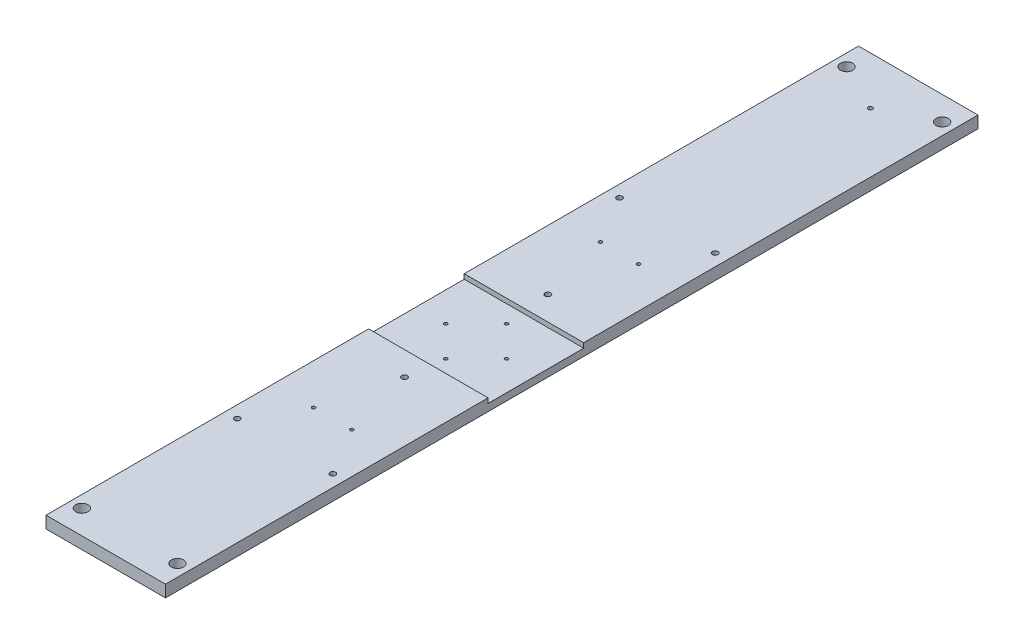
SolidWorks part; units mm, degrees
ref_plane "Front" through (0, 0, 0) normal (0, 0, 1) x (1, 0, 0)
ref_plane "Top" through (0, 0, 0) normal (0, 1, 0) x (1, 0, 0)
ref_plane "Right" through (0, 0, 0) normal (1, 0, 0) x (0, 0, -1)
sketch "Sketch1" plane through (0, 0, 0) normal (0, 1, 0) x (1, 0, 0)
  line L1 (0, 0) -> (63.5, 0)
  line L2 (0, 0) -> (0, 431.8)
  line L3 (0, 431.8) -> (63.5, 431.8)
  line L4 (63.5, 0) -> (63.5, 431.8)
  dimension "D1" = 431.8
  dimension "D2" = 63.5
extrude "Boss-Extrude1" add sketch "Sketch1" along normal blind 6.35
sketch "Sketch3" plane through (0, 6.35, 0) normal (0, 1, 0) x (1, 0, 0)
  line L0 (0, 0) -> (63.5, 0) construction
  line L1 (0, 431.8) -> (0, 0) construction
  line L2 (31.75, 431.8) -> (31.75, 0) construction
  line L3 (63.5, 431.8) -> (0, 431.8) construction
  line L6 (0, 165.1) -> (0, 228.6)
  line L9 (0, 196.85) -> (139.7, 196.85) construction
  circle A0 centre (3.175, 3.175) radius 1.1303
  circle A1 centre (3.175, 161.925) radius 1.1303
  circle A2 centre (3.175, 390.525) radius 1.1303
  circle A3 centre (3.175, 231.775) radius 1.1303
  circle A4 centre (60.325, 3.175) radius 1.1303
  circle A5 centre (60.325, 161.925) radius 1.1303
  circle A6 centre (60.325, 231.775) radius 1.1303
  circle A7 centre (60.325, 390.525) radius 1.1303
  dimension "D1" = 2.2606
  dimension "D2" = 3.175
  dimension "D3" = 3.175
  dimension "D5" = 63.5
  dimension "D4" = 2
sketch "Sketch6" plane through (0, 6.35, 0) normal (0, 1, 0) x (1, 0, 0)
  line L0 (63.5, 431.8) -> (0, 431.8) construction
  line L1 (0, 431.8) -> (0, 0) construction
  line L2 (31.75, 431.8) -> (31.75, 0) construction
  line L3 (0, 0) -> (63.5, 0) construction
  line L4 (31.75, 215.9) -> (94.2364, 215.9) construction
  circle A0 centre (6.35, 419.1) radius 3.2639
  circle A1 centre (57.15, 419.1) radius 3.2639
  circle A4 centre (57.15, 12.7) radius 3.2639
  circle A5 centre (6.35, 12.7) radius 3.2639
  point P13 (31.75, 215.9)
  dimension "D1" = 6.5278
  dimension "D2" = 12.7
  dimension "D3" = 6.35
extrude "Cut-Extrude9" cut sketch "Sketch6" against normal through all
sketch "Sketch7" plane through (0, 6.35, 0) normal (0, 1, 0) x (1, 0, 0)
  line L0 (0, 393.7) -> (63.5, 393.7) construction
  line L1 (0, 431.8) -> (0, 0) construction
  line L2 (63.5, 0) -> (63.5, 431.8) construction
  line L3 (0, 196.85) -> (139.7, 196.85) construction
  line L4 (31.75, 0) -> (31.75, 431.8) construction
  line L5 (0, 196.85) -> (63.5, 196.85) construction
  circle A0 centre (6.35, 298.45) radius 1.4732
  circle A1 centre (3.175, 390.525) radius 1.1303 construction
  circle A2 centre (57.15, 298.45) radius 1.4732
  circle A3 centre (57.15, 95.25) radius 1.4732
  circle A4 centre (6.35, 95.25) radius 1.4732
  circle A5 centre (31.75, 234.95) radius 1.4732
  circle A8 centre (31.75, 158.75) radius 1.4732
  dimension "D1" = 3.175
  dimension "D2" = 101.6
  dimension "D3" = 2.9464
  dimension "D4" = 6.35
  dimension "D5" = 2.9464
  dimension "D6" = 63.5
extrude "Cut-Extrude10" cut sketch "Sketch7" against normal through all
sketch "Sketch8" plane through (0, 6.35, 0) normal (0, 1, 0) x (1, 0, 0)
  line L0 (31.75, 0) -> (31.75, 431.8) construction
  line L1 (0, 196.85) -> (63.5, 196.85) construction
  line L2 (63.5, 0) -> (63.5, 431.8) construction
  circle A0 centre (15.5854, 196.85) radius 0.889
  circle A1 centre (31.75, 213.0146) radius 0.889
  circle A2 centre (47.9146, 196.85) radius 0.889
  circle A3 centre (31.75, 180.6854) radius 0.889
  circle A4 centre (21.59, 273.05) radius 0.889
  circle A5 centre (6.35, 298.45) radius 1.4732 construction
  circle A6 centre (41.91, 273.05) radius 0.889
  circle A7 centre (41.91, 120.65) radius 0.889
  circle A8 centre (21.59, 120.65) radius 0.889
  point P11 (31.75, 196.85)
  point P20 (31.75, 196.85)
  dimension "D1" = 1.778
  dimension "D2" = 16.1646
  dimension "D4" = 1.778
  dimension "D5" = 25.4
  dimension "D6" = 10.16
  dimension "D3" = 4
extrude "Cut-Extrude11" cut sketch "Sketch8" against normal through all
sketch "Sketch9" plane through (0, 6.35, 0) normal (0, 1, 0) x (1, 0, 0)
  line L0 (31.75, 431.8) -> (31.75, 0) construction
  line L1 (31.75, 0) -> (139.7, 196.85) construction
  line L2 (139.7, 196.85) -> (0, 196.85) construction
  line L3 (63.5, 0) -> (63.5, 431.8) construction
  line L4 (0, 171.45) -> (63.5, 171.45)
  line L5 (0, 171.45) -> (0, 222.25)
  line L6 (0, 222.25) -> (63.5, 222.25)
  line L7 (63.5, 171.45) -> (63.5, 222.25)
  line L8 (0, 171.45) -> (63.5, 222.25) construction
  line L9 (0, 222.25) -> (63.5, 171.45) construction
  point P2 (31.75, 196.85)
  dimension "D1" = 50.8
extrude "Cut-Extrude12" cut sketch "Sketch9" against normal blind 2.54
sketch "Sketch10" plane through (0, 6.35, 0) normal (0, 1, 0) x (1, 0, 0)
  line L1 (31.75, 431.8) -> (31.75, 222.25) construction
  line L2 (63.5, 222.25) -> (0, 222.25) construction
  line L3 (63.5, 431.8) -> (0, 431.8) construction
  circle A0 centre (31.75, 406.4) radius 1.1303
  dimension "D1" = 2.2606
  dimension "D2" = 25.4
extrude "Cut-Extrude13" cut sketch "Sketch10" against normal through all
